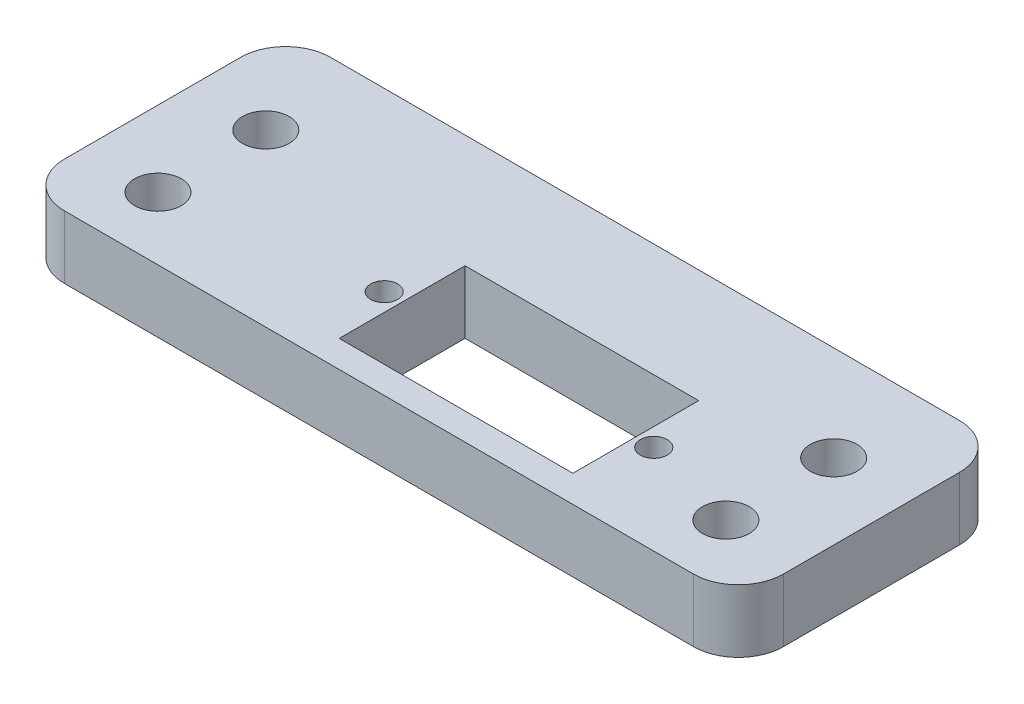
SolidWorks part; units mm, degrees
ref_plane "Front Plane" through (0, 0, 0) normal (0, 0, 1) x (1, 0, 0)
ref_plane "Top Plane" through (0, 0, 0) normal (0, 1, 0) x (1, 0, 0)
ref_plane "Right Plane" through (0, 0, 0) normal (1, 0, 0) x (0, 0, -1)
sketch "Sketch1" plane through (0, 0, 0) normal (0, 1, 0) x (1, 0, 0)
  line L1 (0, 0) -> (101.6, 0)
  line L2 (0, 0) -> (0, 37.592)
  line L3 (0, 37.592) -> (101.6, 37.592)
  line L4 (101.6, 0) -> (101.6, 37.592)
  dimension "D1" = 37.592
  dimension "D2" = 101.6
extrude "Initial Extrude" add sketch "Sketch1" along normal blind 8.89 contours L2 L3 L4 L1
sketch "Sketch2" plane through (0, 8.89, 0) normal (0, 1, 0) x (1, 0, 0)
  line L0 (0, 0) -> (101.6, 0) construction
  line L1 (0, 0) -> (0, 37.592) construction
  line L2 (101.6, 0) -> (101.6, 37.592) construction
  circle A0 centre (10.668, 24.13) radius 3.302
  circle A1 centre (10.668, 8.89) radius 3.302
  circle A2 centre (90.932, 24.13) radius 3.302
  circle A3 centre (90.932, 8.89) radius 3.302
  dimension "D1" = 6.604
  dimension "D2" = 15.24
  dimension "D3" = 8.89
  dimension "D4" = 10.668
  dimension "D5" = 10.668
extrude "Screw Holes" cut sketch "Sketch2" against normal through all contours A1 | A2 | A0 | A3 region at (10.668, 8.89, -8.89) region at (90.932, 8.89, -24.13)
sketch "Sketch4" plane through (0, 8.89, 0) normal (0, 1, 0) x (1, 0, 0)
  line L1 (41.37, 21.59) -> (74.39, 21.59)
  line L2 (41.37, 21.59) -> (41.37, 3.81)
  line L3 (41.37, 3.81) -> (74.39, 3.81)
  line L4 (74.39, 21.59) -> (74.39, 3.81)
  line L5 (101.6, 0) -> (101.6, 37.592) construction
  line L7 (0, 0) -> (101.6, 0) construction
  circle A1 centre (38.83, 12.7) radius 1.905
  circle A2 centre (76.93, 12.7) radius 1.905
  circle A3 centre (65.5, 12.7) radius 8.89
  point P4 (41.37, 12.7)
  point P9 (0, 0)
  point P15 (0, 0)
  dimension "D1" = 38.1
  dimension "D2" = 3.81
  dimension "D3" = 33.02
  dimension "D4" = 17.78
  dimension "D5" = 2.54
  dimension "D6" = 12.7
  dimension "D7" = 36.1
extrude "Servo Rect Hole" cut sketch "Sketch4" against normal through all contours L4 L1 L2 L3 | A2 | A3 | A3 L4 L1 | A3 L3 L4 | A1 region at (50.0587, 8.89, -12.7) region at (72.4043, 8.89, -19.6043) region at (65.5, 8.89, -12.7) region at (72.4043, 8.89, -5.7957) region at (76.93, 8.89, -12.7)
fillet "Fillet1" radius 6.35 4 edges at (101.6, 4.445, -37.592) (101.6, 4.445, 0) (0, 4.445, 0) (0, 4.445, -37.592)
sketch "Sketch6" plane through (0, 0, 0) normal (0, -1, 0) x (-1, 0, 0)
  circle A0 centre (-10.668, 8.89) radius 5.715
  circle A1 centre (-10.668, 24.13) radius 5.715
  circle A2 centre (-90.932, 24.13) radius 5.715
  circle A3 centre (-90.932, 8.89) radius 5.715
  circle A4 centre (-10.668, 24.13) radius 3.302 construction
  circle A6 centre (-90.932, 24.13) radius 3.302 construction
  circle A7 centre (-90.932, 8.89) radius 3.302 construction
  dimension "D1" = 11.43
extrude "Screw Head Hole" cut sketch "Sketch6" against normal blind 3.81
